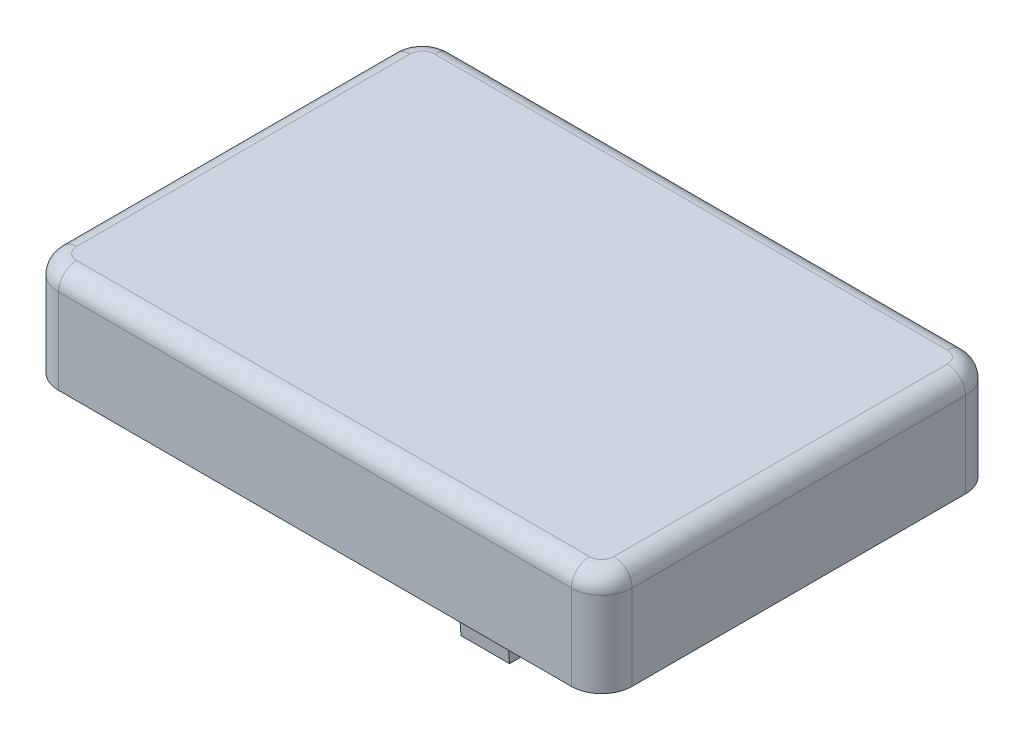
SolidWorks part; units mm, degrees
ref_plane "Front Plane" through (0, 0, 0) normal (0, 0, 1) x (1, 0, 0)
ref_plane "Top Plane" through (0, 0, 0) normal (0, 1, 0) x (1, 0, 0)
ref_plane "Right Plane" through (0, 0, 0) normal (1, 0, 0) x (0, 0, -1)
sketch "Sketch1" plane through (0, 0, 0) normal (0, 1, 0) x (1, 0, 0)
  line L0 (-44.1692, -23.3779) -> (-44.1692, 31.5679)
  line L1 (-39.1692, -26.3779) -> (45.3308, -26.3779)
  line L2 (-42.1692, -23.3779) -> (-42.1692, 31.5679)
  line L3 (-39.1692, 34.5679) -> (45.3308, 34.5679)
  line L4 (48.3308, -23.3779) -> (48.3308, 31.5679)
  line L5 (-42.1692, -26.3779) -> (48.3308, 34.5679) construction
  line L6 (-42.1692, 34.5679) -> (48.3308, -26.3779) construction
  line L7 (-39.1692, 36.5679) -> (45.3308, 36.5679)
  line L8 (50.3308, -23.3779) -> (50.3308, 31.5679)
  line L9 (-39.1692, -28.3779) -> (45.3308, -28.3779)
  line L10 (-44.1692, -5.0821) -> (-44.1692, -18.2821) construction
  line L11 (45.3308, 12.7179) -> (45.3308, 1.7179) construction
  line L12 (-9.4142, 36.5679) -> (3.8358, 36.5679) construction
  line L13 (-33.1692, -23.3779) -> (42.8308, -23.3779) construction
  arc A0 (45.3308, -26.3779) -> (48.3308, -23.3779) centre (45.3308, -23.3779) ccw
  arc A1 (-39.1692, -26.3779) -> (-42.1692, -23.3779) centre (-39.1692, -23.3779) cw
  arc A2 (-42.1692, 31.5679) -> (-39.1692, 34.5679) centre (-39.1692, 31.5679) cw
  arc A3 (45.3308, 34.5679) -> (48.3308, 31.5679) centre (45.3308, 31.5679) cw
  arc A4 (-44.1692, 31.5679) -> (-39.1692, 36.5679) centre (-39.1692, 31.5679) cw
  arc A5 (45.3308, 36.5679) -> (50.3308, 31.5679) centre (45.3308, 31.5679) cw
  arc A6 (45.3308, -28.3779) -> (50.3308, -23.3779) centre (45.3308, -23.3779) ccw
  arc A7 (-39.1692, -28.3779) -> (-44.1692, -23.3779) centre (-39.1692, -23.3779) cw
  point P0 (0, 0)
  dimension "D1" = 3
  dimension "D3" = 3
  dimension "D4" = 3
  dimension "D2" = 2
extrude "Boss-Extrude1" add sketch "Sketch1" along normal blind 1.5 contours A7 L9 A6 L8 A5 L7 A4 L0 L3 A3 L4 A0 L1 A1 L2 A2 | L3 A3 L4 A0 L1 A1 L2 A2 region at (-43.0226, 0, -4.095)
extrude "Boss-Extrude2" add sketch "Sketch1<3>" against normal up to surface (15.53 mm away)
sketch "Sketch1<3>" plane through (0, 0, 0) normal (0, 1, 0) x (1, 0, 0) same geometry as "Sketch1"
sketch "Sketch2" plane through (0, 0, -36.5679) normal (0, 0, -1) x (-1, 0, 0)
  line L5 (-34.8158, -2) -> (25.1542, -2)
  line L6 (-34.8158, -2) -> (-34.8158, -16.03)
  line L7 (-34.8158, -16.03) -> (25.1542, -16.03)
  line L30 (25.1542, -2) -> (25.1542, -16.03)
  line L36 (-21.0658, -3) -> (-34.3158, -3) construction
  line L37 (-34.3158, -15.53) -> (-34.3158, -3) construction
  line L40 (-21.0658, -15.53) -> (-34.3158, -15.53) construction
  line L41 (24.6542, -15.53) -> (24.6542, -3) construction
  point P1 (-18.3894, -2)
  point P4 (27.5699, -16.03)
  point P5 (-40.8036, -17.2336)
  point P6 (27.5731, -2)
  point P17 (-16.8994, -3)
  point P18 (-32.597, -2.4283)
  point P22 (-44.0078, -3)
  point P23 (-18.8894, -3)
  point P25 (-18.523, -2)
  point P26 (-32.1394, -3)
  dimension "D2" = 1
  dimension "D3" = 0.5
  dimension "D6" = 0.5
  dimension "D1" = 0.5
extrude "Cut-Extrude1" cut sketch "Sketch2" against normal up to next
fillet "Fillet1" radius 3 16 edges at (-42.7047, 1.5, -35.1034) (-44.1692, 1.5, -4.095) (-42.7047, 1.5, 26.9134) (3.0808, 1.5, 28.3779) (48.8663, 1.5, 26.9134) (50.3308, 1.5, -4.095) (48.8663, 1.5, -35.1034) (3.0808, 1.5, -36.5679) (-41.2905, 0, 25.4992) (-42.1692, 0, -4.095) (-41.2905, 0, -33.6892) (3.0808, 0, -34.5679) (47.4521, 0, -33.6892) (48.3308, 0, -4.095) (47.4521, 0, 25.4992) (3.0808, 0, 26.3779)
ref_plane "Plane1" through (25, 0, 0) normal (1, 0, 0) x (0, 0, -1)
sketch "Sketch8" plane through (25, 0, 0) normal (1, 0, 0) x (0, 0, -1)
  line L1 (-24.3779, -15.2539) -> (-24.3779, -19.53)
  line L2 (-24.3779, -19.53) -> (-26.2279, -19.53)
  line L3 (-26.2279, -19.53) -> (-26.5279, -15.53)
  line L4 (-26.5279, -15.53) -> (-26.5279, -11.53)
  line L5 (-26.3779, -15.53) -> (-26.3779, -3) construction
  line L6 (-26.5279, -11.53) -> (-24.3779, -15.2539)
  line L7 (-26.5279, -15.53) -> (-26.3779, -15.53) construction
  point P2 (0, 0)
  point P8 (-26.0651, -19.53)
  point P10 (-24.3779, -15.436)
  point P12 (-26.5279, -11.9462)
  dimension "D1" = 2
  dimension "D2" = 0.15
  dimension "D3" = 4
  dimension "D4" = 0.15
  dimension "D5" = 30
  dimension "D6" = 4
extrude "Boss-Extrude4" add sketch "Sketch8" along normal blind 8 contours L3 L4 L6 L1 L2
